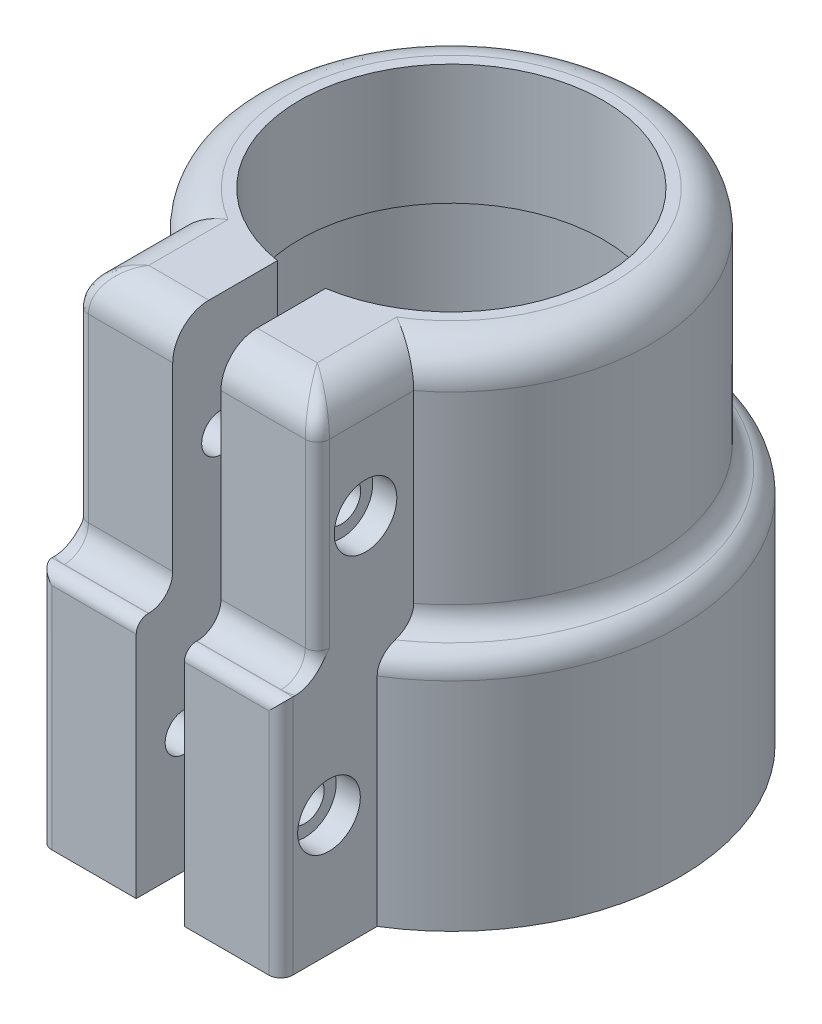
SolidWorks part; units mm, degrees
ref_plane "Front Plane" through (0, 0, 0) normal (0, 0, 1) x (1, 0, 0)
ref_plane "Top Plane" through (0, 0, 0) normal (0, 1, 0) x (1, 0, 0)
ref_plane "Right Plane" through (0, 0, 0) normal (1, 0, 0) x (0, 0, -1)
sketch "Sketch1" plane through (0, 0, 0) normal (0, 1, 0) x (1, 0, 0)
  circle A0 centre (0, 0) radius 19
  dimension "D1" = 38
extrude "Boss-Extrude1" add sketch "Sketch1" along normal blind 20
sketch "Sketch2" plane through (0, 20, 0) normal (0, 1, 0) x (1, 0, 0)
  circle A0 centre (0, 0) radius 16.5
  dimension "D1" = 33
extrude "Boss-Extrude2" add sketch "Sketch2" along normal blind 20
sketch "Sketch3" plane through (0, 0, 0) normal (0, -1, 0) x (1, 0, 0)
  circle A0 centre (0, 0) radius 15.1
  dimension "D1" = 30.2
extrude "Cut-Extrude1" cut sketch "Sketch3" against normal blind 30
sketch "Sketch4" plane through (0, 40, 0) normal (0, 1, 0) x (1, 0, 0)
  circle A0 centre (0, 0) radius 12.6
  dimension "D1" = 25.2
extrude "Cut-Extrude2" cut sketch "Sketch4" against normal up to next
sketch "Sketch5" plane through (0, 0, 0) normal (0, -1, 0) x (-1, 0, 0)
  line L1 (10, -24.1555) -> (-10, -24.1555)
  line L2 (10, -24.1555) -> (10, -16.1555)
  line L4 (-10, -24.1555) -> (-10, -16.1555)
  arc A2 (-10, -16.1555) -> (10, -16.1555) centre (0, 0) ccw
  dimension "D5" = 19
  dimension "D1" = 20
  dimension "D2" = 10
  dimension "D4" = 8
extrude "Boss-Extrude3" add sketch "Sketch5" against normal up to surface (20 mm away) up to face at (0, 20, 16.5)
sketch "Sketch6" plane through (0, 40, 0) normal (0, 1, 0) x (1, 0, 0)
  line L0 (10, -21.1244) -> (10, -13.1244)
  line L1 (10, -16.1555) -> (10, -24.1555) construction
  line L2 (10, -21.1244) -> (-10, -21.1244)
  line L3 (-10, -24.1555) -> (-10, -16.1555) construction
  line L4 (-10, -21.1244) -> (-10, -13.1244)
  arc A0 (-10, -13.1244) -> (10, -13.1244) centre (0, 0) ccw
  dimension "D1" = 8
extrude "Boss-Extrude4" add sketch "Sketch6" against normal up to surface (20 mm away) up to face at (0, 20, 16.5)
sketch "Sketch7" plane through (0, 40, 0) normal (0, 1, 0) x (1, 0, 0)
  line L1 (2, -27.7711) -> (-2, -27.7711)
  line L2 (2, -27.7711) -> (2, -7.8656)
  line L3 (2, -7.8656) -> (-2, -7.8656)
  line L4 (-2, -27.7711) -> (-2, -7.8656)
  dimension "D1" = 4
  dimension "D2" = 2
extrude "Cut-Extrude3" cut sketch "Sketch7" against normal through all
fillet "Fillet1" radius 3 5 edges at (-6, 40, 21.1244) (6, 40, 21.1244) (-10, 40, 17.1244) (10, 40, 17.1244) (0, 40, -16.5)
fillet "Fillet3" radius 1 8 edges at (-9.1213, 39.1213, 20.2457) (9.1213, 39.1213, 20.2457) (6, 20, 24.1555) (-6, 20, 24.1555) (-10, 28.5, 21.1244) (-10, 10, 24.1555) (10, 10, 24.1555) (10, 28.5, 21.1244)
fillet "Fillet4" radius 2 1 edges at (0, 20, -19)
fillet "Fillet5" radius 2 4 edges at (-9.7071, 20, 20.8315) (9.7071, 20, 20.8315) (-5.5, 20, 21.1244) (5.5, 20, 21.1244)
fillet "Fillet6" radius 2 1 edges at (0, 20, -16.5)
sketch "Sketch8" plane through (10, 0, 0) normal (1, 0, 0) x (0, 0, -1)
  line L0 (-21.1244, 22) -> (-21.1244, 37) construction
  line L1 (-24.1555, 0) -> (-24.1555, 19) construction
  line L2 (-18.1244, 40) -> (-11.5434, 40) construction
  line L4 (-16.1555, 0) -> (-23.1555, 0) construction
  circle A0 centre (-20.1555, 10) radius 1.6
  circle A2 centre (-17.1244, 30) radius 1.6
  dimension "D7" = 3.2
  dimension "D10" = 3.2
  dimension "D1" = 4
  dimension "D4" = 4
  dimension "D5" = 10
  dimension "D12" = 10
extrude "Cut-Extrude4" cut sketch "Sketch8" against normal up to surface (20 mm away) up to face at (-10, 19.4904, 18.2786)
sketch "Sketch9" plane through (10, 0, 0) normal (1, 0, 0) x (0, 0, -1)
  circle A0 centre (-17.1244, 30) radius 2.6
  circle A3 centre (-20.1555, 10) radius 2.6
  dimension "D1" = 5.2
  dimension "D4" = 5.2
extrude "Cut-Extrude5" cut sketch "Sketch9" against normal blind 2
sketch "Sketch10" plane through (-10, 0, 0) normal (-1, 0, 0) x (0, 0, 1)
  line L1 (17.1244, 33.2332) -> (14.3244, 31.6166)
  line L2 (14.3244, 31.6166) -> (14.3244, 28.3834)
  line L3 (14.3244, 28.3834) -> (17.1244, 26.7668)
  line L4 (17.1244, 26.7668) -> (19.9244, 28.3834)
  line L5 (19.9244, 28.3834) -> (19.9244, 31.6166)
  line L6 (19.9244, 31.6166) -> (17.1244, 33.2332)
  line L19 (20.1555, 6.7668) -> (22.9555, 8.3834)
  line L20 (22.9555, 8.3834) -> (22.9555, 11.6166)
  line L21 (22.9555, 11.6166) -> (20.1555, 13.2332)
  line L22 (20.1555, 13.2332) -> (17.3555, 11.6166)
  line L23 (17.3555, 11.6166) -> (17.3555, 8.3834)
  line L24 (17.3555, 8.3834) -> (20.1555, 6.7668)
  circle A0 centre (17.1244, 30) radius 2.8 construction
  circle A3 centre (20.1555, 10) radius 2.8 construction
  dimension "D1" = 5.6
  dimension "D4" = 5.6
extrude "Cut-Extrude6" cut sketch "Sketch10" against normal blind 3
